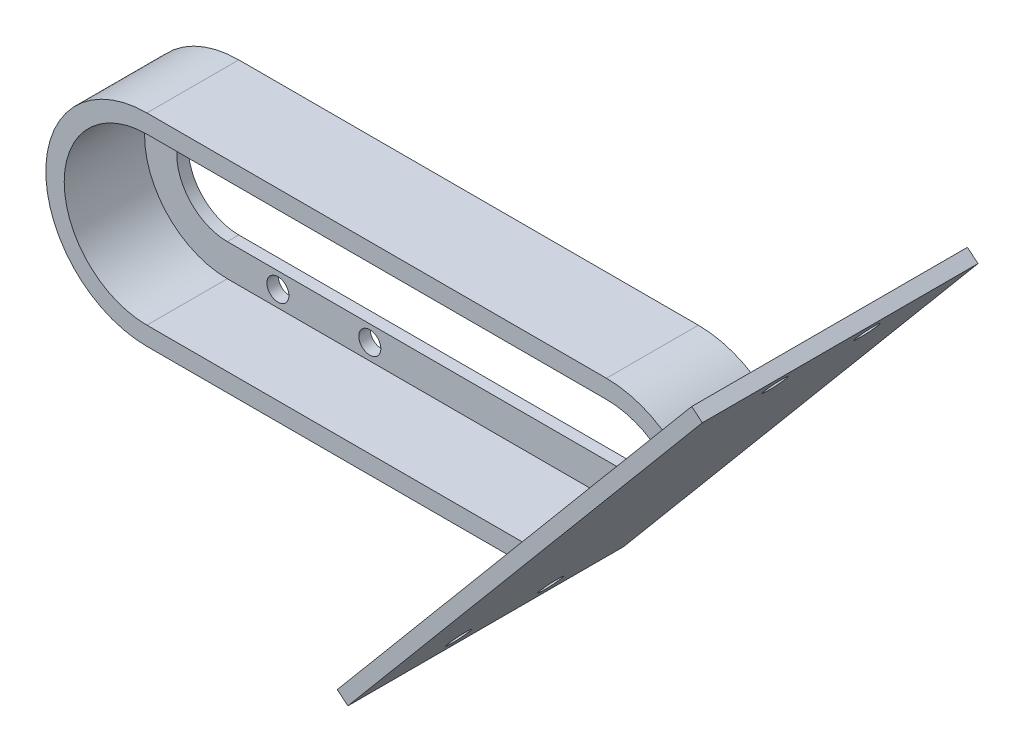
SolidWorks part; units mm, degrees
ref_plane "Front Plane" through (0, 0, 0) normal (0, 0, 1) x (1, 0, 0)
ref_plane "Top Plane" through (0, 0, 0) normal (0, 1, 0) x (1, 0, 0)
ref_plane "Right Plane" through (0, 0, 0) normal (1, 0, 0) x (0, 0, -1)
sketch "Sketch1" plane through (0, 0, 0) normal (0, 0, 1) x (1, 0, 0)
  line L0 (-21, 0) -> (79, 0) construction
  line L1 (-21, 11) -> (21, 11)
  line L2 (-21, 11) -> (-21, -11)
  line L3 (-21, -11) -> (21, -11)
  line L4 (21, 11) -> (21, -11)
  line L5 (-21, 11) -> (21, -11) construction
  line L6 (-21, -11) -> (21, 11) construction
  line L9 (-21, 11) -> (79, 11)
  line L10 (-21, -11) -> (79, -11)
  line L11 (-21, 0) -> (79, 0) construction
  line L12 (-21, 18) -> (79, 18)
  line L13 (-21, -18) -> (79, -18)
  line L14 (-21, 0) -> (79, 0) construction
  line L19 (-21, 22) -> (79, 22)
  line L20 (-21, -22) -> (79, -22)
  line L22 (-10, 14.5) -> (10, 14.5)
  line L23 (-10, 14.5) -> (-10, -14.5)
  line L24 (-10, -14.5) -> (10, -14.5)
  line L25 (10, 14.5) -> (10, -14.5)
  line L26 (-10, 14.5) -> (10, -14.5) construction
  line L27 (-10, -14.5) -> (10, 14.5) construction
  line L31 (79, 0) -> (-21, 0)
  line L32 (40.4327, -45.9627) -> (117.5673, 45.9627)
  line L33 (40.4327, -45.9627) -> (42.7309, -47.891)
  line L34 (42.7309, -47.891) -> (119.8654, 44.0343)
  line L35 (117.5673, 45.9627) -> (119.8654, 44.0343)
  line L36 (40.4327, -45.9627) -> (119.8654, 44.0343) construction
  line L37 (42.7309, -47.891) -> (117.5673, 45.9627) construction
  arc A2 (-21, 11) -> (-21, -11) centre (-21, 0) ccw
  arc A3 (79, -11) -> (79, 11) centre (79, 0) ccw
  arc A4 (-21, 18) -> (-21, -18) centre (-21, 0) ccw
  arc A5 (79, -18) -> (79, 18) centre (79, 0) ccw
  arc A6 (-21, 22) -> (-21, -22) centre (-21, 0) ccw
  arc A7 (79, -22) -> (79, 22) centre (79, 0) ccw
  circle A8 centre (-10, -14.5) radius 2.4
  circle A9 centre (10, -14.5) radius 2.4
  circle A10 centre (10, 14.5) radius 2.4
  circle A11 centre (-10, 14.5) radius 2.4
  point P0 (0, 0)
  point P8 (29, 0)
  point P15 (29, 0)
  point P22 (29, 0)
  point P27 (0, 0)
  point P36 (80.1491, -0.9642)
  point P48 (0, 0)
  point P49 (224.2685, 58.5749)
  point P50 (228.061, 49.7005)
  point P51 (79, 0)
  dimension "D1" = 42
  dimension "D3" = 100
  dimension "D4" = 18
  dimension "D5" = 100
  dimension "D6" = 100
  dimension "D7" = 22
  dimension "D10" = 4.8
  dimension "D11" = 4.8
  dimension "D12" = 4.8
  dimension "D13" = 4.8
  dimension "D2" = 22
  dimension "D8" = 29
  dimension "D9" = 20
  dimension "D14" = 3
  dimension "D15" = 120
  dimension "D16" = 50
extrude "Boss-Extrude1" add sketch "Sketch1" along normal blind 2.5 contours L13 A5 L12 A4 A11 L22 A10 L25 L1 L9 A3 L10 L3 A9 L24 A8 L23 A2 | A11 L23 L9 L25 A10 L22 | A9 L25 L10 L23 A8 L24 region at (-33.3448, 0, 0) region at (0, 12.6414, 0) region at (0, -12.6414, 0)
extrude "Boss-Extrude2" add sketch "Sketch1<3>" along normal blind 20 contours L20 A7 L19 A6 A5 L13 A4 L12 region at (85.6457, 18.2589, 0)
sketch "Sketch1<3>" plane through (0, 0, 0) normal (0, 0, 1) x (1, 0, 0) same geometry as "Sketch1"
extrude "Boss-Extrude3" add sketch "Sketch1<4>" along normal blind 40 contours L34 A3 L32 L10 | L34 A5 L32 A3 | L34 A7 L32 A5 | A7 L34 L35 L32 | L33 L34 L20 L32 | L20 L34 L13 L32 | L13 L34 L10 L32 region at (79.3992, -1.8102, 0) region at (89.4023, 10.0543, 0) region at (68.7912, -14.5, 0) region at (92.958, 14.2964, 0) region at (64.1761, -20, 0) region at (106.4824, 30.4165, 0) region at (52.0599, -34.4696, 0)
sketch "Sketch1<4>" plane through (0, 0, 0) normal (0, 0, 1) x (1, 0, 0) same geometry as "Sketch1"
extrude "Boss-Extrude4" add sketch "Sketch1<5>" against normal blind 20 contours L33 L34 L20 L32 | A7 L34 L35 L32 | L34 A5 L32 A3 | L34 A7 L32 A5 | L34 A3 L32 L10 | L13 L34 L10 L32 | L20 L34 L13 L32 region at (79.3992, -1.8102, 0) region at (89.4023, 10.0543, 0) region at (68.7912, -14.5, 0) region at (92.958, 14.2964, 0) region at (64.1761, -20, 0) region at (106.4824, 30.4165, 0) region at (52.0599, -34.4696, 0)
sketch "Sketch1<5>" plane through (0, 0, 0) normal (0, 0, 1) x (1, 0, 0) same geometry as "Sketch1"
sketch "Sketch5" plane through (48.6572, -40.8283, 0) normal (0.766, -0.6428, 0) x (0, 0, -1)
  line L0 (0, 110.7802) -> (20, 110.7802)
  line L5 (-40, -2.8198) -> (-20, -2.8198)
  line L6 (-40, -2.8198) -> (-40, -9.2198)
  line L7 (-40, -9.2198) -> (-20, -9.2198)
  line L8 (-20, -2.8198) -> (-20, -9.2198)
  line L9 (-40, -2.8198) -> (-20, -9.2198) construction
  line L10 (-40, -9.2198) -> (-20, -2.8198) construction
  line L11 (0, 110.7802) -> (0, 104.3802)
  line L12 (0, 104.3802) -> (20, 104.3802)
  line L13 (20, 110.7802) -> (20, 104.3802)
  line L14 (0, 110.7802) -> (20, 104.3802) construction
  line L15 (0, 104.3802) -> (20, 110.7802) construction
  line L16 (-40, 110.7802) -> (-20, 110.7802)
  line L17 (-40, 110.7802) -> (-40, 104.3802)
  line L18 (-40, 104.3802) -> (-20, 104.3802)
  line L19 (-20, 110.7802) -> (-20, 104.3802)
  line L20 (-40, 110.7802) -> (-20, 104.3802) construction
  line L21 (-40, 104.3802) -> (-20, 110.7802) construction
  line L22 (0, -2.8198) -> (20, -2.8198)
  line L23 (0, -2.8198) -> (0, -9.2198)
  line L24 (0, -9.2198) -> (20, -9.2198)
  line L25 (20, -2.8198) -> (20, -9.2198)
  line L26 (0, -2.8198) -> (20, -9.2198) construction
  line L27 (0, -9.2198) -> (20, -2.8198) construction
  line L28 (-40, -9.2198) -> (20, -9.2198) construction
  line L29 (-40, -9.2198) -> (-40, 110.7802) construction
  line L30 (20, -9.2198) -> (20, 110.7802) construction
  line L31 (-40, 110.7802) -> (20, 110.7802) construction
  circle A0 centre (-20, 104.3802) radius 2.4
  circle A1 centre (0, -2.8198) radius 2.4
  circle A2 centre (0, 104.3802) radius 2.4
  circle A3 centre (-20, -2.8198) radius 2.4
  point P0 (-30, -6.0198)
  point P5 (10, 107.5802)
  point P10 (-30, 107.5802)
  point P15 (10, -6.0198)
  point P30 (0, 0)
  point P35 (-97.0507, 56.1431)
  point P38 (-92.9459, 43.2644)
  dimension "D9" = 4.8
  dimension "D10" = 4.8
  dimension "D11" = 4.8
  dimension "D12" = 4.8
  dimension "D13" = 4.8
  dimension "D14" = 4.8
  dimension "D1" = 20
  dimension "D2" = 6.4
  dimension "D3" = 6.4
  dimension "D4" = 20
  dimension "D5" = 20
  dimension "D6" = 6.4
  dimension "D7" = 20
  dimension "D8" = 6.4
extrude "Cut-Extrude1" cut sketch "Sketch5" against normal blind 3 from surface contours L8 A3 L5 | L5 A3 L8 | L22 A1 L23 | L23 A1 L22 | L18 A0 L19 | L19 A0 L18 | L11 A2 L12 | L12 A2 L11 region at (116.4063, 39.9119, -1.0186) region at (115.5333, 38.8715, 0.3395) region at (47.063, -42.7282, 19.6605) region at (46.19, -43.7686, 21.0186) region at (115.5333, 38.8715, 19.6605) region at (116.4063, 39.9119, 21.0186) region at (47.063, -42.7282, 0.3395) region at (46.19, -43.7686, -1.0186) starting at face at (81.2981, -1.9284, 10)
